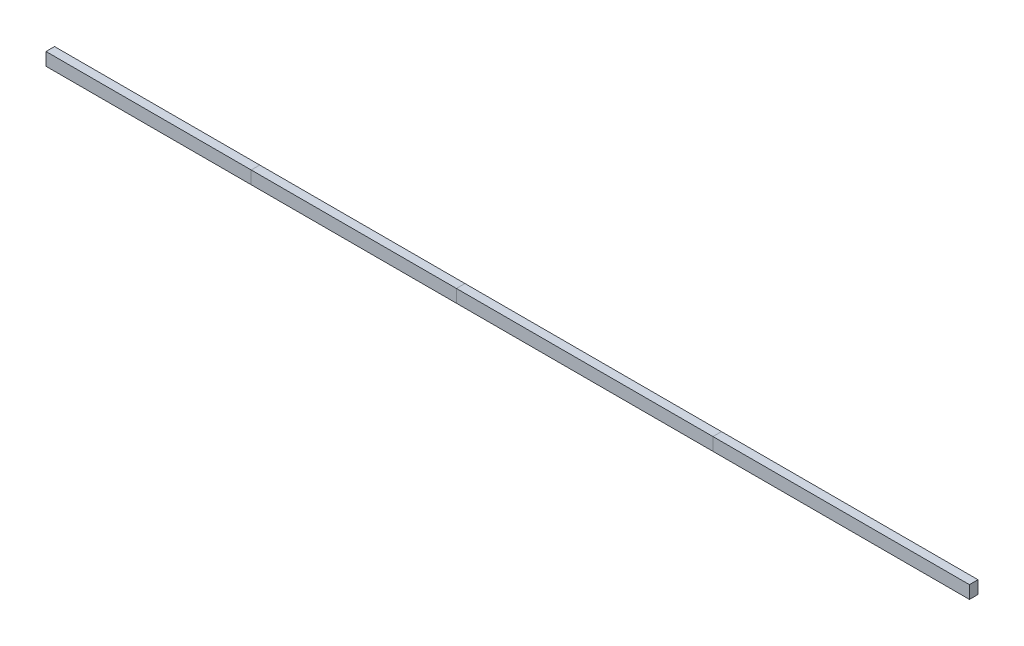
SolidWorks part; units mm, degrees
material "7075-T6 (SN)"
ref_plane "Front Plane" through (0, 0, 0) normal (0, 0, 1) x (1, 0, 0)
ref_plane "Top Plane" through (0, 0, 0) normal (0, 1, 0) x (1, 0, 0)
ref_plane "Right Plane" through (0, 0, 0) normal (1, 0, 0) x (0, 0, -1)
sketch "Sketch1" plane through (0, 0, 0) normal (0, 0, 1) x (1, 0, 0)
  line L0 (0, 0) -> (1219.2, 0)
  line L1 (1219.2, 0) -> (2438.4, 0)
  line L2 (2438.4, 0) -> (3962.4, 0)
  line L3 (3962.4, 0) -> (5486.4, 0)
  point P4 (0, 0)
  point P7 (0, 0)
  point P8 (0, 0)
  point P9 (0, 0)
  point P10 (0, 0)
  point P11 (0, 0)
  point P12 (0, 0)
  point P13 (0, 0)
  point P14 (0, 0)
  point P15 (0, 0)
  point P16 (0, 0)
  point P17 (0, 0)
  point P18 (0, 0)
  dimension "D1" = 1219.2
  dimension "D2" = 1219.2
  dimension "D3" = 5486.4
  dimension "D4" = 1524
sketch "Sketch2" plane through (0, 0, 0) normal (1, 0, 0) x (0, 0, -1)
  line L1 (-25.4, -38.1) -> (25.4, -38.1)
  line L2 (-25.4, -38.1) -> (-25.4, 38.1)
  line L3 (-25.4, 38.1) -> (25.4, 38.1)
  line L4 (25.4, -38.1) -> (25.4, 38.1)
  line L5 (-25.4, -38.1) -> (25.4, 38.1) construction
  line L6 (-25.4, 38.1) -> (25.4, -38.1) construction
  point P0 (0, 0)
  dimension "D1" = 50.8
  dimension "D2" = 76.2
extrude "Boss-Extrude1" add sketch "Sketch2" along normal up to vertex (1219.2 mm away) up to point (1219.2, 0, 0)
extrude "Boss-Extrude5" add sketch "Sketch2<8>" along normal up to vertex (2438.4 mm away) from vertex separate body up to point (2438.4, 0, 0) starting at point (1219.2, 0, 0)
sketch "Sketch2<8>" plane through (0, 0, 0) normal (1, 0, 0) x (0, 0, -1) same geometry as "Sketch2"
extrude "Boss-Extrude6" add sketch "Sketch2<9>" along normal up to vertex (3962.4 mm away) from vertex separate body up to point (3962.4, 0, 0) starting at point (2438.4, 0, 0)
sketch "Sketch2<9>" plane through (0, 0, 0) normal (1, 0, 0) x (0, 0, -1) same geometry as "Sketch2"
extrude "Boss-Extrude7" add sketch "Sketch2<10>" along normal up to vertex (5486.4 mm away) from vertex separate body up to point (5486.4, 0, 0) starting at point (3962.4, 0, 0)
sketch "Sketch2<10>" plane through (0, 0, 0) normal (1, 0, 0) x (0, 0, -1) same geometry as "Sketch2"
